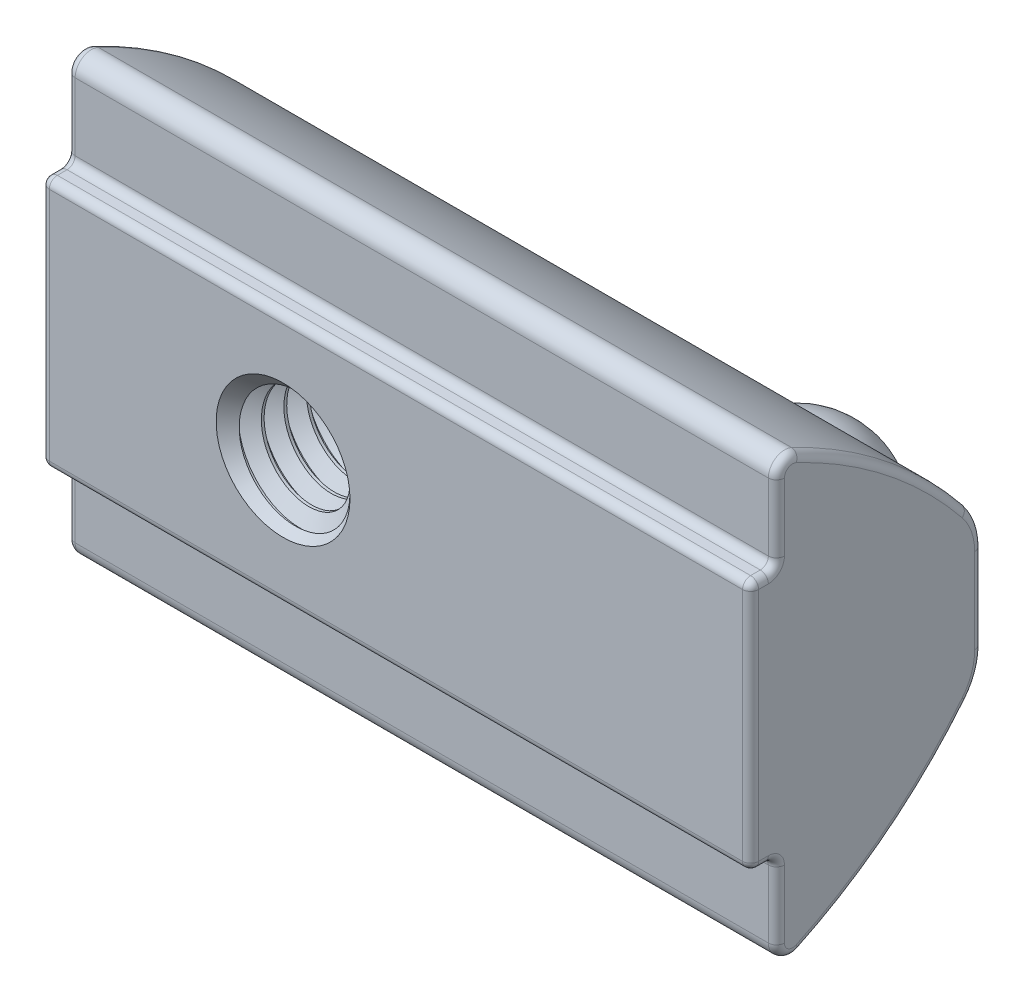
SolidWorks part; units mm, degrees
ref_plane "Front Plane" through (0, 0, 0) normal (0, 0, 1) x (1, 0, 0)
ref_plane "Top Plane" through (0, 0, 0) normal (0, 1, 0) x (1, 0, 0)
ref_plane "Right Plane" through (0, 0, 0) normal (1, 0, 0) x (0, 0, -1)
sketch "Sketch1" plane through (0, 0, 0) normal (0, 0, 1) x (1, 0, 0)
  line L0 (0, 6.75) -> (0, -6.75) construction
  line L1 (-11, 6.75) -> (11, 6.75) construction
  line L2 (-11, 6.75) -> (-11, -6.75) construction
  line L3 (-11, -6.75) -> (11, -6.75) construction
  line L4 (11, 6.75) -> (11, -6.75) construction
  line L5 (-11, 0) -> (11, 0) construction
  circle A1 centre (-3.5, 0) radius 2 construction
  point P5 (0, 0)
  point P12 (-3.5, -2)
  point P14 (-3.5, 2)
  dimension "Thread Diameter" = 4
  dimension "Length" = 22
  dimension "Width" = 13.5
  dimension "D3" = 7.5
sketch "Sketch2" plane through (0, 0, 0) normal (1, 0, 0) x (0, 0, -1)
  line L0 (-3.6, 0) -> (3.6, 0) construction
  line L1 (-4.2562, 2.0758) -> (-3.9062, 1.4696)
  line L2 (-3.6, 3.9) -> (-3.6, -3.9) construction
  line L3 (-3.9062, 1.4696) -> (-3.5562, 2.0758)
  line L4 (-3.5562, 2.0758) -> (-4.2562, 2.0758)
  line L5 (-3.9062, 2.0758) -> (-3.9062, 2)
  line L6 (-3.9062, 1.4696) -> (-3.9062, 1.5453)
  line L7 (-4.2125, 2) -> (-3.6, 2)
  line L8 (-4.2344, 2.0379) -> (-3.5781, 2.0379)
  line L9 (-3.95, 1.5453) -> (-3.8625, 1.5453)
  point P3 (0, 0)
  point P6 (-3.6, 0)
  point P7 (-2.8, 0)
  point P8 (5.35, 0)
  point P9 (-3.6, -2)
  point P11 (-3.6, 2)
  point P22 (-3.9062, 2)
  point P25 (-3.9062, 2.0379)
  point P28 (-3.9062, 1.5453)
  dimension "D1" = 7.8
  dimension "D2" = 0.8
  dimension "Thickness" = 7.2
  dimension "Ball Offset" = 1.75
  dimension "Thread Pitch" = 0.7
  dimension "D6" = 0.0875
sketch "Sketch3" plane through (0, 0, 0) normal (1, 0, 0) x (0, 0, -1)
  line L0 (-3.6, 3.9) -> (-2.8, 3.9)
  line L1 (-2.8, 3.9) -> (-2.8, 6.245)
  line L2 (-3.6, 3.9) -> (-3.6, -3.9)
  line L3 (-3.6, -3.9) -> (-2.8, -3.9)
  line L4 (-2.8, -3.9) -> (-2.8, -6.245)
  line L7 (3.6, 1.3212) -> (3.6, -1.3212)
  arc A0 (-2.0784, 6.7012) -> (3.1556, 2.5781) centre (-8.5116, -6.8492) cw
  arc A1 (-2.0784, -6.7012) -> (3.1556, -2.5781) centre (-8.5116, 6.8492) ccw
  arc A4 (-2.0784, -6.7012) -> (-2.8, -6.245) centre (-2.295, -6.245) cw
  arc A5 (-2.8, 6.245) -> (-2.0784, 6.7012) centre (-2.295, 6.245) cw
  arc A6 (3.1556, -2.5781) -> (3.6, -1.3212) centre (1.6, -1.3212) ccw
  arc A7 (3.6, 1.3212) -> (3.1556, 2.5781) centre (1.6, 1.3212) ccw
  point P20 (3.6, -2)
  point P23 (3.6, 2)
  point P32 (-2.295, 6.75)
  dimension "D1" = 0.505
  dimension "D2" = 15
  dimension "D4" = 2
  dimension "D3" = 4
extrude "Boss-Extrude1" add sketch "Sketch3" against normal up to vertex (11 mm away) and the other way up to vertex (11 mm away) up to point (-11, 0, 0) other way up to point (11, 6.75, 0)
sketch "Sketch4" plane through (0, 0, -3.6) normal (0, 0, -1) x (-1, 0, 0)
  line L0 (11, 0) -> (-11, 0) construction
  circle A0 centre (-6, 0) radius 2.5
  dimension "D1" = 5
  dimension "D2" = 9.5
extrude "Cut-Extrude1" cut sketch "Sketch4" against normal blind 5
ref_plane "Plane1" through (6, 0, 0) normal (1, 0, 0) x (0, 0, -1)
sketch "Sketch5" plane through (6, 0, 0) normal (1, 0, 0) x (0, 0, -1)
  line L0 (3.6, -2.5) -> (3.6, 2.5) construction
  line L1 (3.6, -2.5) -> (3.6, 2.5) construction
  line L2 (-3.6, 0) -> (3.6, 0) construction
  line L3 (0.35, 0) -> (5.35, 0)
  arc A0 (5.35, 0) -> (0.35, 0) centre (2.85, 0) ccw
  point P9 (2.85, 2.5)
revolve "Revolve1" add sketch "Sketch5" angle 360 about L3
sketch "Sketch6" plane through (0, 0, 3.6) normal (0, 0, 1) x (1, 0, 0)
  circle A0 centre (-3.5, 0) radius 2 construction
  circle A1 centre (-3.5, 0) radius 2
extrude "Cut-Extrude2" cut sketch "Sketch6" against normal through all
sketch "Sketch7" plane through (0, 0, -3.6) normal (0, 0, -1) x (-1, 0, 0)
  circle A0 centre (3.5, 0) radius 3
  dimension "D1" = 6
extrude "Cut-Extrude3" cut sketch "Sketch7" against normal through all draft 45
fillet "Fillet3" radius 0.25 28 edges at (-11, 0, -3.6) (-11, -4.934, -0.7704) (-11, 4.934, -0.7704) (-11, -6.6718, 2.5649) (-11, 6.6718, 2.5649) (-11, -5.0725, 2.8) (-11, 5.0725, 2.8) (11, -5.0725, 2.8) (11, -6.6718, 2.5649) (11, -4.934, -0.7704) (11, 0, -3.6) (11, 5.0725, 2.8) (11, 6.6718, 2.5649) (-11, -3.9, 3.2) (0, -3.9, 3.6) (11, -3.9, 3.2) (0, -3.9, 2.8) (-11, 3.9, 3.2) (0, 3.9, 2.8) (11, 3.9, 3.2) (0, 3.9, 3.6) (-11, 0, 3.6) (11, 0, 3.6) (11, 4.934, -0.7704) (-11, -1.9878, -3.4856) (-11, 1.9878, -3.4856) (11, -1.9878, -3.4856) (11, 1.9878, -3.4856)
sketch "Sketch8" plane through (0, 0, 0) normal (0, 0, 1) x (1, 0, 0)
  line L0 (-3.5, 0) -> (-2.0858, -1.4142)
  line L1 (-11, 0) -> (11, 0) construction
  circle A0 centre (-3.5, 0) radius 2 construction
  circle A1 centre (-3.5, 0) radius 2
  point P0 (-11, 6.75)
  point P1 (11, 6.75)
  point P3 (-11, -6.75)
  point P13 (-2.0858, -1.4142)
  dimension "D1" = 45
sketch "Sketch9" plane through (0, 0, 0) normal (1, 0, 0) x (0, 0, -1)
  line L0 (3.6, -2.5) -> (3.6, 2.5) construction
  line L1 (3.6, -2.5) -> (3.6, 2.5)
  point P0 (-3.6, 3.9)
  point P1 (3.6, 2.5)
  point P2 (-3.6, -3.9)
  point P7 (5.35, 0)
ref_plane "Plane2" through (-3.5, 0, 0) normal (1, 0, 0) x (0, 0, -1)
sketch "Sketch10" plane through (0, 0, 3.6) normal (0, 0, 1) x (1, 0, 0)
  circle A0 centre (-3.5, 0) radius 2 construction
  circle A1 centre (-3.5, 0) radius 2
curve "Helix/Spiral1" pitch 0.7 height 7.9 radius 2 centre (-3.5, 0, 3.6) axis (0, 0, -1) start towards (0, 1, 0)
sketch "Sketch11" plane through (-3.5, 0, 0) normal (1, 0, 0) x (0, 0, -1)
  line L0 (-3.95, 1.5453) -> (-3.8625, 1.5453) construction
  line L1 (-3.9062, 1.4696) -> (-3.5562, 2.0758) construction
  line L2 (-4.2562, 2.0758) -> (-3.9062, 1.4696) construction
  line L3 (-4.2344, 2.0379) -> (-3.5781, 2.0379) construction
  line L4 (-3.95, 1.5453) -> (-3.8625, 1.5453)
  line L5 (-3.8625, 1.5453) -> (-3.5781, 2.0379)
  line L6 (-4.2344, 2.0379) -> (-3.95, 1.5453)
  line L7 (-4.2344, 2.0379) -> (-3.5781, 2.0379)
sweep "Sweep1" add profiles "Sketch11" path "Helix/Spiral1"
sketch "Sketch12" plane through (0, 0, 3.6) normal (0, 0, 1) x (1, 0, 0)
  circle A0 centre (-3.5, 0) radius 2.0758
  point P4 (-3.5, 2.0758)
extrude "Cut-Extrude4" cut sketch "Sketch12" along normal through all and the other way through all draft 45
sketch "Sketch13" plane through (0, 0, -3.6) normal (0, 0, -1) x (-1, 0, 0)
  circle A1 centre (3.5, 0) radius 3
  circle A2 centre (3.5, 0) radius 3
  dimension "D1" = 0
extrude "Cut-Extrude5" cut sketch "Sketch13" along normal through all and the other way through all draft 45
equation "\"D6@Sketch2\" = \"Thread Pitch@Sketch2\" / 8"
equation "\"D1@Sketch7\"=\"Thread Diameter@Sketch1\"*1.5"
equation "\"D3@Helix/Spiral1\" = \"Thickness@Sketch2\" + \"Thread Pitch@Sketch2\""
equation "\"D4@Helix/Spiral1\" = \"Thread Pitch@Sketch2\""
